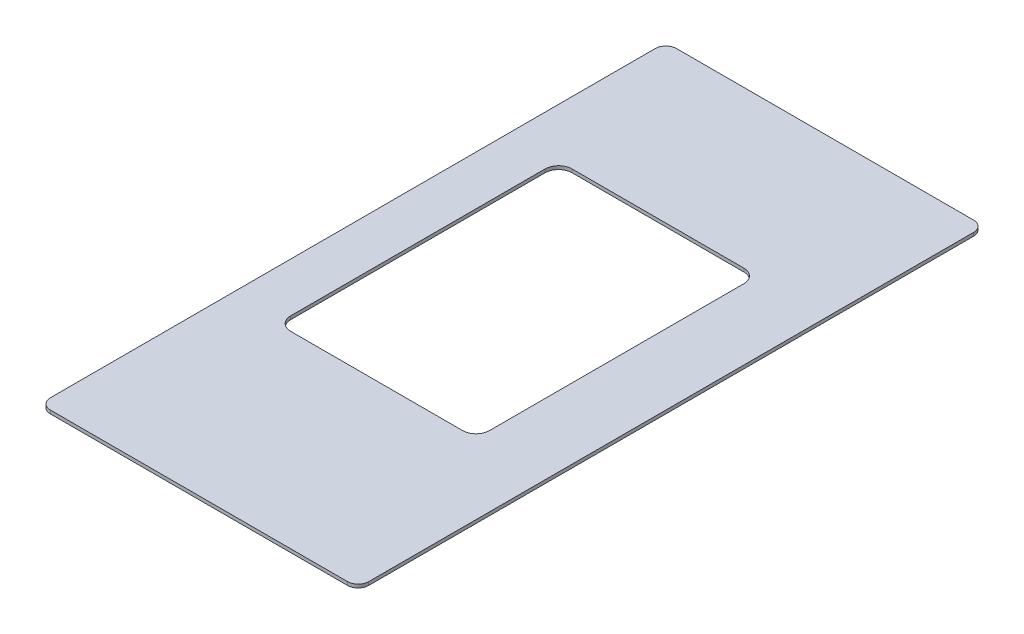
SolidWorks part; units mm, degrees
material "5052-H32"
ref_plane "Front Plane" through (0, 0, 0) normal (0, 0, 1) x (1, 0, 0)
ref_plane "Top Plane" through (0, 0, 0) normal (0, 1, 0) x (1, 0, 0)
ref_plane "Right Plane" through (0, 0, 0) normal (1, 0, 0) x (0, 0, -1)
sketch "Sketch9" plane through (0, 0, 0) normal (0, 1, 0) x (1, 0, 0)
  line L0 (-130, 0) -> (130, 0) construction
  line L1 (-130, 550) -> (130, 550) construction
  line L2 (-130, 550) -> (-130, 0) construction
  line L4 (130, 550) -> (130, 0) construction
  line L14 (83.6625, 157.4438) -> (-103.6625, 157.4438)
  line L15 (-150, 570) -> (150, 570)
  line L16 (150, 570) -> (150, -20)
  line L17 (-150, -20) -> (150, -20)
  line L18 (-150, 570) -> (-150, -20)
  line L19 (-10, 290) -> (155.5075, 290) construction
  line L20 (83.6625, 157.4438) -> (83.6625, 422.5563)
  line L21 (83.6625, 422.5563) -> (-103.6625, 422.5563)
  line L22 (-103.6625, 157.4438) -> (-103.6625, 422.5563)
  line L23 (83.6625, 157.4438) -> (-103.6625, 422.5563) construction
  line L24 (83.6625, 422.5563) -> (-103.6625, 157.4438) construction
  line L25 (-130, 0) -> (130, 0) construction
  point P5 (-10, 290)
  point P19 (0, 0)
  dimension "D10" = 550
  dimension "D9" = 260
  dimension "D3" = 265.1125
  dimension "D4" = 187.325
  dimension "D5" = 260
  dimension "D6" = 140
  dimension "D2" = 20
extrude "Boss-Extrude7" add sketch "Sketch9" along normal blind 3.175 separate body contours L15 L18 L17 L16 region at (0, 0, -563.3811)
fillet "Fillet4" radius 10 4 edges at (-150, 1.5875, -570) (150, 1.5875, -570) (-150, 1.5875, 20) (150, 1.5875, 20)
sketch "Sketch10" plane through (0, 0, 0) normal (0, 1, 0) x (1, 0, 0)
  line L0 (0, 0) -> (0, 500) construction
  line L1 (-130, 500) -> (130, 500) construction
  line L2 (-130, 500) -> (-130, 0) construction
  line L3 (-130, 0) -> (130, 0) construction
  line L4 (130, 500) -> (130, 0) construction
  line L8 (-150, 520) -> (-150, -20) construction
  line L9 (-150, -20) -> (150, -20) construction
  line L10 (150, 520) -> (150, -20) construction
  line L11 (-150, 520) -> (150, 520) construction
  line L15 (130, 250) -> (-130, 250) construction
  circle A0 centre (-140, -10) radius 2.5
  circle A2 centre (-140, 42) radius 2.5
  circle A3 centre (-140, 94) radius 2.5
  circle A4 centre (-140, 146) radius 2.5
  circle A5 centre (-140, 198) radius 2.5
  circle A6 centre (-140, 250) radius 2.5
  circle A7 centre (-140, 302) radius 2.5
  circle A8 centre (-140, 354) radius 2.5
  circle A9 centre (-140, 406) radius 2.5
  circle A10 centre (-140, 458) radius 2.5
  circle A16 centre (-140, 510) radius 2.5
  circle A17 centre (-83, 510) radius 2.5
  circle A18 centre (-26, 510) radius 2.5
  circle A19 centre (31, 510) radius 2.5
  circle A20 centre (88, 510) radius 2.5
  circle A21 centre (145, 510) radius 2.5
  circle A22 centre (145, 458) radius 2.5
  circle A23 centre (145, 406) radius 2.5
  circle A24 centre (145, 354) radius 2.5
  circle A25 centre (145, 302) radius 2.5
  circle A26 centre (145, 250) radius 2.5
  circle A27 centre (145, 198) radius 2.5
  circle A28 centre (145, 146) radius 2.5
  circle A29 centre (145, 94) radius 2.5
  circle A30 centre (145, 42) radius 2.5
  circle A31 centre (145, -10) radius 2.5
  circle A38 centre (89, -10) radius 2.5
  circle A39 centre (33, -10) radius 2.5
  circle A40 centre (-23, -10) radius 2.5
  circle A41 centre (-79, -10) radius 2.5
  dimension "D4" = 5
  dimension "D7" = 5
  dimension "D2" = 10
  dimension "D3" = 10
  dimension "D5" = 6
  dimension "D6" = 11
  dimension "D8" = 11
  dimension "D9" = 260
  dimension "D1" = 20
fillet "Fillet5" radius 12.7 4 edges at (-103.6625, 1.5875, -157.4438) (83.6625, 1.5875, -157.4438) (83.6625, 1.5875, -422.5563) (-103.6625, 1.5875, -422.5563)
extrude "Bolt Holes" [suppressed] cut sketch "Sketch10" along normal up to next
equation "\"W\"= 260"
equation "\"D9@Sketch9\"=\"W\""
equation "\"L\"= 550"
equation "\"D10@Sketch9\"=\"L\""
equation "\"Offset\"= 20"
equation "\"D2@Sketch9\"=\"Offset\""
equation "\"D5@Sketch9\"=\"L\"/2-15"
equation "\"D6@Sketch9\"=\"W\"/2+10"
